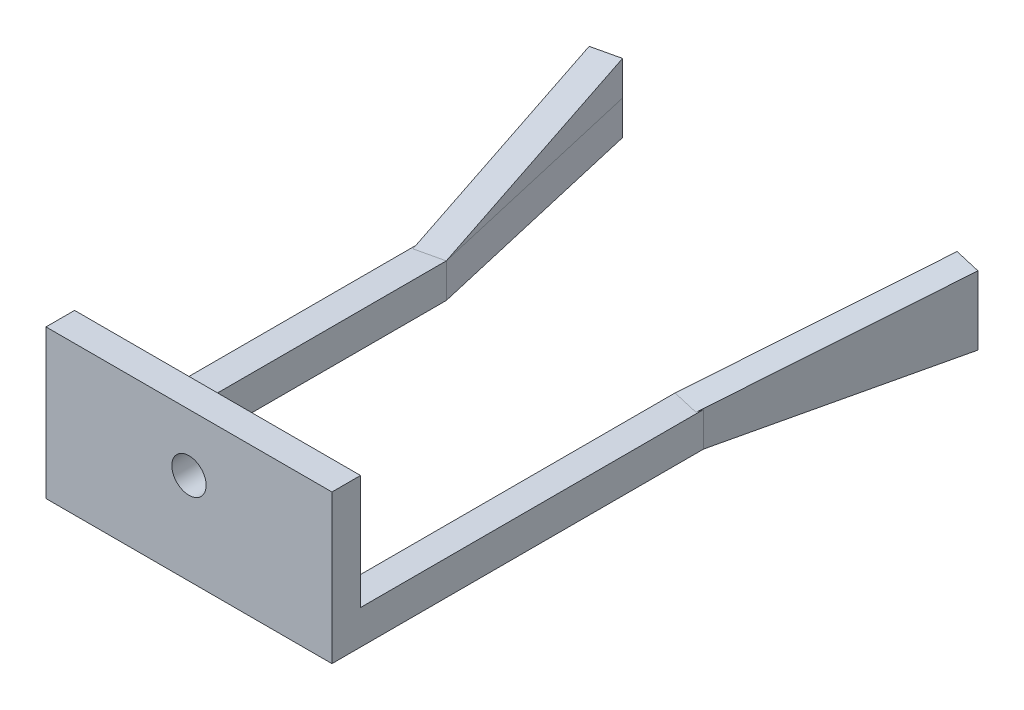
SolidWorks part; units mm, degrees
ref_plane "Front Plane" through (0, 0, 0) normal (0, 0, 1) x (1, 0, 0)
ref_plane "Top Plane" through (0, 0, 0) normal (0, 1, 0) x (1, 0, 0)
ref_plane "Right Plane" through (0, 0, 0) normal (1, 0, 0) x (0, 0, -1)
sketch "Sketch1" plane through (0, 0, 0) normal (0, 1, 0) x (1, 0, 0)
  line L0 (0, -55) -> (0, 55) construction
  line L6 (-12.5, -2.5) -> (12.5, -2.5)
  line L12 (10, 0) -> (10, 30)
  line L15 (-10, 0) -> (-10, 30)
  line L16 (-10, 0) -> (10, 0)
  line L17 (-12.5, 30) -> (-12.5, -2.5)
  line L18 (12.5, -2.5) -> (12.5, 30)
  line L19 (-10, 30) -> (-14.6255, 50.0354)
  line L20 (-14.6255, 50.0354) -> (-16.999, 49.4874)
  line L21 (-16.999, 49.4874) -> (-12.5, 30)
  line L22 (14.6255, 50.0354) -> (16.999, 49.4874)
  line L23 (16.999, 49.4874) -> (12.5, 30)
  line L24 (10, 30) -> (14.6255, 50.0354)
  point P0 (0, 0)
  dimension "D1" = 20
  dimension "D2" = 2.5
  dimension "D3" = 2.5
  dimension "D4" = 20
  dimension "D5" = 167
  dimension "D6" = 30
extrude "Boss-Extrude1" add sketch "Sketch1" along normal blind 3
sketch "Sketch2" plane through (-2.9184, 0, 0.6738) normal (0.9744, 0, -0.225) x (-0.225, 0, -0.9744)
  line L0 (31.4806, 3) -> (52.043, 6)
  line L1 (52.043, 6) -> (52.043, 3)
  line L2 (31.4806, 3) -> (52.043, 3) construction
  line L3 (31.4806, 3) -> (52.043, 3)
  dimension "D1" = 3
extrude "Boss-Extrude2" add sketch "Sketch2" against normal up to surface (2.4359 mm away) separate body up to face at (-14.7495, 1.5, -39.7437)
mirror "Mirror4" about plane through (0, 0, 0) normal (1, 0, 0) of "Boss-Extrude2"
fillet "Fillet1" [suppressed] radius 2
sketch "Sketch3" plane through (0, 3, 0) normal (0, 1, 0) x (1, 0, 0)
  line L0 (12.5, -2.5) -> (12.5, 30) construction
  line L1 (-12.5, -2.5) -> (12.5, -2.5)
  line L2 (-12.5, -2.5) -> (-12.5, 0)
  line L3 (-12.5, 0) -> (12.5, 0)
  line L4 (12.5, -2.5) -> (12.5, 0)
  line L5 (10, 0) -> (-10, 0) construction
extrude "Boss-Extrude3" add sketch "Sketch3" along normal blind 10
sketch "Sketch4" plane through (0, 0, 0) normal (0, 0, -1) x (-1, 0, 0)
  line L0 (12.5, 13) -> (12.5, 3) construction
  circle A0 centre (0, 8) radius 1.5
  point P4 (12.5, 8)
  dimension "D1" = 3
extrude "Cut-Extrude1" cut sketch "Sketch4" against normal through all
